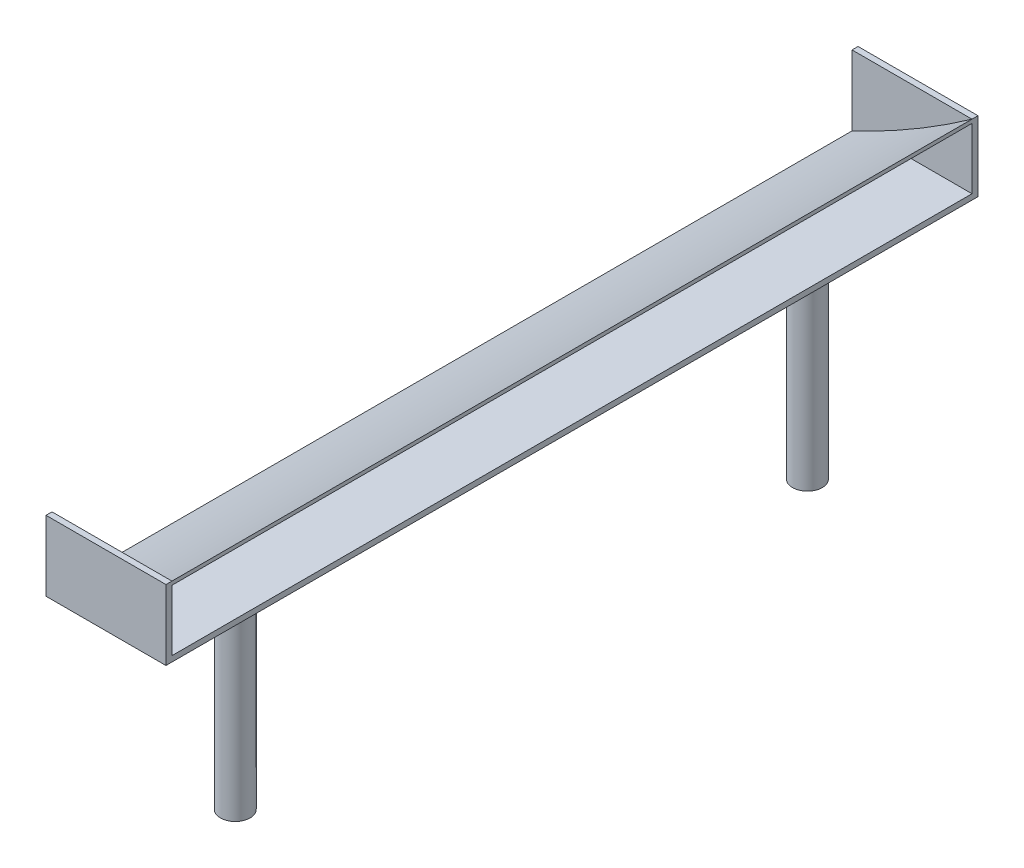
SolidWorks part; units mm, degrees
ref_plane "Front Plane" through (0, 0, 0) normal (0, 0, 1) x (1, 0, 0)
ref_plane "Top Plane" through (0, 0, 0) normal (0, 1, 0) x (1, 0, 0)
ref_plane "Right Plane" through (0, 0, 0) normal (1, 0, 0) x (0, 0, -1)
sketch "Sketch1" plane through (0, 0, 0) normal (0, 0, 1) x (1, 0, 0)
  line L0 (156.4292, 112.402) -> (156.4292, 106.3293)
  line L2 (-43.5708, -4.5349) -> (-36.7183, -4.5349)
  spline S0 degree 2 poles (-43.5708, -4.5349) (61.566, 45.125) (156.4292, 112.402) knots 0 0 0 1 1 1
  spline S1 degree 2 poles (-36.7183, -4.5349) (65.3431, 41.2659) (156.4292, 106.3293) knots 0 0 0 1 1 1
extrude "Boss-Extrude1" add sketch "Sketch1" along normal blind 672 and the other way blind 672
sketch "Sketch2" plane through (0, 0, 672) normal (0, 0, 1) x (1, 0, 0)
  line L1 (-43.5708, -4.5349) -> (156.4292, -4.5349)
  line L2 (-43.5708, -4.5349) -> (-43.5708, 112.402)
  line L3 (-43.5708, 112.402) -> (156.4292, 112.402)
  line L4 (156.4292, -4.5349) -> (156.4292, 112.402)
extrude "Boss-Extrude2" add sketch "Sketch2" against normal blind 10 contours L2 L3 L4 L1
sketch "Sketch3" plane through (0, 0, 662) normal (0, 0, -1) x (-1, 0, 0)
  line L1 (-156.4292, -4.5349) -> (10.1829, -4.5349)
  line L2 (-156.4292, -4.5349) -> (-156.4292, 4.729)
  line L3 (-156.4292, 4.729) -> (10.1829, 4.729)
  line L4 (10.1829, -4.5349) -> (10.1829, 4.729)
extrude "Boss-Extrude4" add sketch "Sketch3" along normal blind 1344 contours L3 L4 L1 L2
sketch "Sketch4" plane through (0, 0, -682) normal (0, 0, -1) x (-1, 0, 0)
  line L1 (-156.4292, -4.5349) -> (43.5708, -4.5349)
  line L2 (-156.4292, -4.5349) -> (-156.4292, 112.402)
  line L3 (-156.4292, 112.402) -> (43.5708, 112.402)
  line L4 (43.5708, -4.5349) -> (43.5708, 112.402)
extrude "Boss-Extrude5" add sketch "Sketch4" against normal blind 10
sketch "Sketch5" plane through (0, -4.5349, 0) normal (0, -1, 0) x (1, 0, 0)
  line L0 (-43.5708, 672) -> (156.4292, 672) construction
  line L1 (156.4292, -682) -> (-43.5708, -682) construction
  circle A0 centre (72.0432, 472) radius 24.75
  circle A1 centre (72.0432, -482) radius 24.75
  dimension "D1" = 49.5
  dimension "D2" = 49.5
  dimension "D3" = 200
  dimension "D4" = 200
extrude "Boss-Extrude6" add sketch "Sketch5" along normal blind 350
